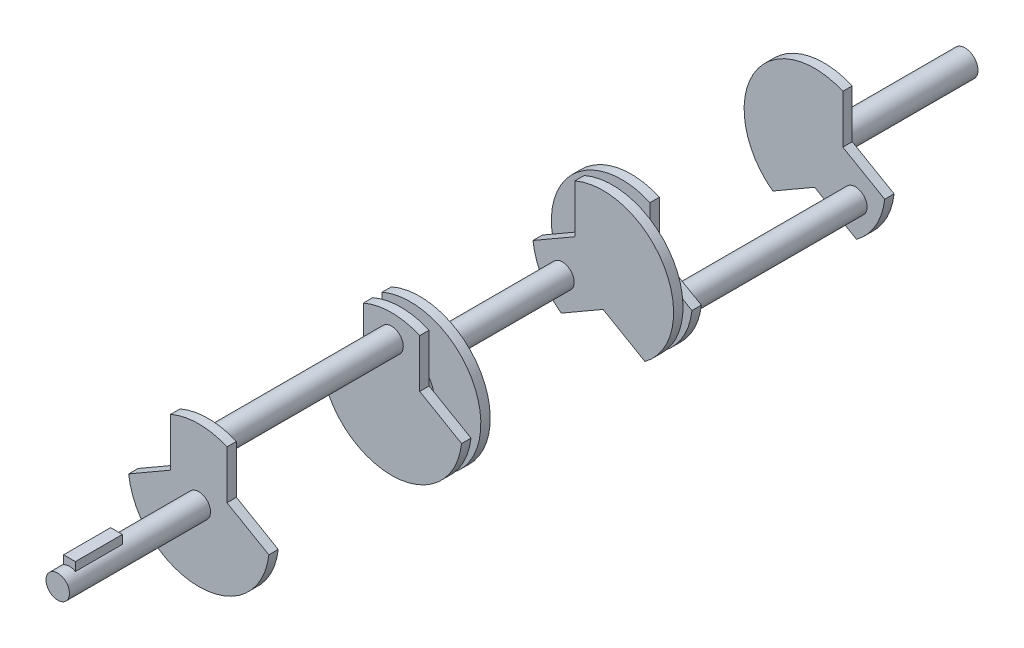
SolidWorks part; units mm, degrees
note: The reader was unsure of these and kept them because the rebuilt part matched: shared geometry of "Sketch3<2>".
ref_plane "Front Plane" through (0, 0, 0) normal (0, 0, 1) x (1, 0, 0)
ref_plane "Top Plane" through (0, 0, 0) normal (0, 1, 0) x (1, 0, 0)
ref_plane "Right Plane" through (0, 0, 0) normal (1, 0, 0) x (0, 0, -1)
sketch "Sketch1" plane through (0, 0, 0) normal (0, 0, 1) x (1, 0, 0)
  line L0 (0, 0) -> (0, 38.1) construction
  line L1 (0, 0) -> (32.9956, -19.05) construction
  line L2 (0, 0) -> (-32.9956, -19.05) construction
  line L3 (15.24, 8.7988) -> (15.24, 34.9192)
  line L4 (-15.24, 8.7988) -> (-15.24, 34.9192)
  line L5 (15.24, 8.7988) -> (37.8609, -4.2614)
  line L6 (-15.24, 8.7988) -> (-37.8609, -4.2614)
  line L7 (-7.62, 13.1982) -> (-40.6156, -5.8518) construction
  line L8 (-15.24, 0) -> (-15.24, 38.1) construction
  line L9 (15.24, 0) -> (15.24, 38.1) construction
  line L10 (7.62, 13.1982) -> (40.6156, -5.8518) construction
  arc A0 (-37.8609, -4.2614) -> (37.8609, -4.2614) centre (0, 0) ccw
  arc A1 (15.24, 34.9192) -> (-15.24, 34.9192) centre (0, 0) ccw
  dimension "D1" = 76.2
  dimension "D2" = 120
  dimension "D3" = 120
  dimension "D4" = 15.24
  dimension "D5" = 15.24
  dimension "D6" = 15.24
  dimension "D7" = 15.24
extrude "Boss-Extrude1" add sketch "Sketch1" against normal blind 5.08
pattern_linear "LPattern1" count 2 spacing 104.14 along (0, 0, -1) of bodies 101
sketch "Sketch2" plane through (0, 0, -5.08) normal (0, 0, -1) x (-1, 0, 0)
  line L0 (0, 25.4) -> (0, 0) construction
  circle A0 centre (0, 25.4) radius 6.35
  dimension "D2" = 12.7
  dimension "D1" = 25.4
extrude "Boss-Extrude2" add sketch "Sketch2" along normal up to next
pattern_linear "LPattern2" count 3 spacing 114.3 along (0, 0, -1) of bodies 103
move or copy body "Body-Move/Copy1" bodies to move or copy 104 copy no rotation origin (0, 0, 0) rotation axis (0, 0, 1) rotation angle 120
move or copy body "Body-Move/Copy2" bodies to move or copy 105 copy no rotation origin (0, 0, 0) rotation axis (0, 0, -1) rotation angle 120
sketch "Sketch3" plane through (0, 0, -109.22) normal (0, 0, -1) x (-1, 0, 0)
  circle A0 centre (0, 0) radius 12.7
  dimension "D1" = 25.4
extrude "Boss-Extrude3" add sketch "Sketch3" along normal up to next
extrude "Boss-Extrude4" add sketch "Sketch3<2>" along normal up to next from surface
sketch "Sketch3<2>" plane through (0, 0, -109.22) normal (0, 0, -1) x (-1, 0, 0) same geometry as "Sketch3"
sketch "Sketch4" plane through (0, 0, -337.82) normal (0, 0, -1) x (-1, 0, 0)
  circle A0 centre (0, 0) radius 6.985
  dimension "D1" = 13.97
extrude "Boss-Extrude5" add sketch "Sketch4" along normal blind 76.2
sketch "Sketch5" plane through (0, 0, 0) normal (0, 0, 1) x (1, 0, 0)
  circle A0 centre (0, 0) radius 6.35
  dimension "D1" = 12.7
extrude "Boss-Extrude6" add sketch "Sketch5" along normal blind 76.2
sketch "Sketch6" plane through (0, 0, 0) normal (0, 1, 0) x (1, 0, 0)
  line L0 (0, 0) -> (0, -44.45) construction
  line L1 (-3.175, -44.45) -> (3.175, -44.45)
  line L2 (-3.175, -44.45) -> (-3.175, -69.85)
  line L3 (-3.175, -69.85) -> (3.175, -69.85)
  line L4 (3.175, -44.45) -> (3.175, -69.85)
  dimension "D1" = 44.45
  dimension "D2" = 25.4
  dimension "D3" = 6.35
extrude "Boss-Extrude7" add sketch "Sketch6" along normal up to surface (4.6607 mm away) from offset 10.16
